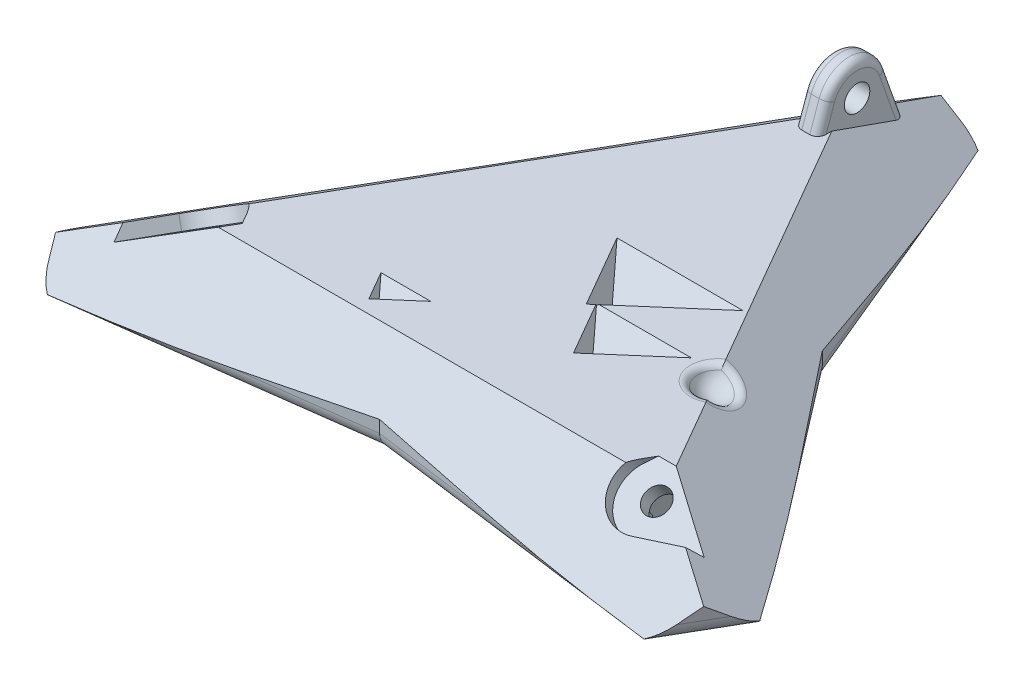
SolidWorks part; units mm, degrees
ref_plane "Front Plane" through (0, 0, 0) normal (0, 0, 1) x (1, 0, 0)
ref_plane "Top Plane" through (0, 0, 0) normal (0, 1, 0) x (1, 0, 0)
ref_plane "Right Plane" through (0, 0, 0) normal (1, 0, 0) x (0, 0, -1)
sketch "Sketch2" plane through (0, 0, 0) normal (0, 1, 0) x (1, 0, 0)
  line L0 (0, 57.735) -> (-50, -28.8675)
  line L1 (-50, -28.8675) -> (50, -28.8675)
  line L2 (50, -28.8675) -> (0, 57.735)
  line L3 (0, 0) -> (0, 57.735) construction
  line L4 (50, -28.8675) -> (0, 0) construction
  line L5 (0, 0) -> (-50, -28.8675) construction
  line L6 (0, 0) -> (0, -28.8675) construction
  line L7 (0, 0) -> (25, 14.4338) construction
  line L8 (0, 0) -> (-25, 14.4338) construction
  line L9 (10, 40.4145) -> (0, 34.641) construction
  line L10 (0, 34.641) -> (-10, 40.4145) construction
  dimension "D1" = 20
sketch "Sketch3" plane through (0, 0, 0) normal (1, 0, 0) x (0, 0, -1)
  line L0 (-28.8675, 0) -> (-19.245, 27.2166) construction
  line L1 (-19.245, 27.2166) -> (0, 20.4124) construction
  line L2 (0, 20.4124) -> (-28.8675, 0) construction
  line L3 (-19.245, 27.2166) -> (-28.983, -0.3266) construction
  line L4 (-28.983, -0.3266) -> (0.2309, 20.3308)
  line L5 (0.2309, 20.3308) -> (-19.245, 27.2166)
  line L6 (-28.983, -0.3266) -> (-28.983, 27.2166)
  line L7 (-28.983, 27.2166) -> (-19.245, 27.2166)
  line L8 (0, 0) -> (0, 103.8474) construction
  dimension "D1" = 0.2
ref_plane "Plane1" through (0, 0, 0) normal (0.5, 0, 0.866) x (0.866, 0, -0.5)
sketch "Sketch4" plane through (0, 0, 0) normal (0.5, 0, 0.866) x (0.866, 0, -0.5)
  line L0 (0, 20.4124) -> (19.245, 27.2166) construction
  line L1 (19.245, 27.2166) -> (28.8675, 0) construction
  line L2 (28.8675, 0) -> (0, 20.4124) construction
  line L3 (0, 81.6497) -> (0, 0) construction
  line L4 (-0.2309, 20.3308) -> (19.245, 27.2166)
  line L5 (19.245, 27.2166) -> (28.983, -0.3266) construction
  line L6 (28.983, -0.3266) -> (-0.2309, 20.3308)
  line L7 (19.245, 27.2166) -> (28.983, 27.2166)
  line L8 (28.983, 27.2166) -> (28.983, -0.3266)
  dimension "D1" = 0.2
ref_plane "Plane2" through (0, 0, 0) normal (0.5, 0, -0.866) x (-0.866, 0, -0.5)
sketch "Sketch5" plane through (0, 0, 0) normal (0.5, 0, -0.866) x (-0.866, 0, -0.5)
  line L0 (19.245, 27.2166) -> (0, 20.4124) construction
  line L1 (0, 20.4124) -> (28.8675, 0) construction
  line L2 (28.8675, 0) -> (19.245, 27.2166) construction
  line L3 (19.245, 27.2166) -> (-0.2309, 20.3308)
  line L4 (-0.2309, 20.3308) -> (28.983, -0.3266)
  line L5 (28.983, -0.3266) -> (19.245, 27.2166) construction
  line L6 (19.245, 27.2166) -> (28.983, 27.2166)
  line L7 (28.983, 27.2166) -> (28.983, -0.3266)
  dimension "D1" = 0.2
extrude "Boss-Extrude1" add sketch "Sketch2" along normal up to vertex (20.4124 mm away) up to point (0, 20.4124, 0)
extrude "Cut-Extrude2" cut sketch "Sketch3" against normal up to vertex (50 mm away) from vertex at 50 starting at point (50, 0, 28.8675)
extrude "Cut-Extrude3" cut sketch "Sketch4" along normal through all and the other way through all
extrude "Cut-Extrude4" cut sketch "Sketch5" along normal through all from vertex at -50 starting at point (-50, 0, 28.8675)
sketch "Sketch6" plane through (0, 0, 0) normal (0, 1, 0) x (1, 0, 0)
  line L0 (0, 0) -> (40.7397, -23.5211) construction
  line L1 (0, 0) -> (-40.7397, -23.5211) construction
  line L2 (0, 0) -> (0, -23.5211) construction
  line L3 (0, 0) -> (0, 47.0422) construction
  line L4 (0, 0) -> (-20.3699, 11.7606) construction
  line L5 (0, 0) -> (20.3699, 11.7606) construction
  line L6 (0, 0) -> (25, 14.4338) construction
  line L7 (50, -28.8675) -> (0, 0) construction
  line L8 (49.4, -28.5211) -> (0, 57.0422) construction
  line L9 (40.7397, -23.5211) -> (37.853, -28.5211) construction
  line L10 (0, 57.0422) -> (-49.4, -28.5211) construction
  line L11 (-49.4, -28.5211) -> (49.4, -28.5211) construction
  line L12 (37.853, -28.5211) -> (0, -23.5211)
  line L13 (0, -23.5211) -> (-37.853, -28.5211)
  line L14 (-37.853, -28.5211) -> (-40.7397, -23.5211) construction
  line L15 (-40.7397, -23.5211) -> (-43.6265, -18.5211) construction
  line L16 (-43.6265, -18.5211) -> (-20.3699, 11.7606)
  line L18 (5.7735, 47.0422) -> (-5.7735, 47.0422)
  line L19 (-37.853, -28.5211) -> (-43.6265, -18.5211)
  line L21 (20.3699, 11.7606) -> (43.6265, -18.5211)
  line L22 (43.6265, -18.5211) -> (40.7397, -23.5211) construction
  line L23 (0, 57.0422) -> (49.4, -28.5211) construction
  line L24 (0, 0) -> (0, 57.735) construction
  line L27 (43.6265, -18.5211) -> (37.853, -28.5211)
  line L35 (50, -28.8675) -> (0, 57.735) construction
  line L36 (50, -28.8675) -> (0, 57.735) construction
  line L37 (0, 57.735) -> (-50, -28.8675) construction
  line L38 (0, 57.735) -> (-50, -28.8675) construction
  line L46 (20.3699, 11.7606) -> (5.7735, 47.0422)
  line L47 (-5.7735, 47.0422) -> (-20.3699, 11.7606)
  circle A0 centre (0, 0) radius 47.0422 construction
  circle A1 centre (0, 0) radius 23.5211 construction
  circle A2 centre (0, 0) radius 57.0422 construction
  dimension "D1" = 10
  dimension "D2" = 5
extrude "Cut-Extrude5" cut sketch "Sketch6" along normal through all flip side to cut
sketch "Sketch7" plane through (0, 0, 0) normal (1, 0, 0) x (0, 0, -1)
  line L0 (31.2288, 11.3333) -> (27.2218, 0) construction
  line L1 (35.7071, 0) -> (27.2218, 0) construction
  line L3 (31.2288, 11.3333) -> (27.2218, 0)
  line L4 (42.7782, 0) -> (27.2218, 0)
  line L5 (38.7712, 11.3333) -> (42.7782, 0)
  line L6 (35, 10) -> (35, 0) construction
  arc A0 (38.7712, 8.6667) -> (31.2288, 11.3333) centre (35, 10) ccw construction
  arc A1 (38.7712, 11.3333) -> (31.2288, 11.3333) centre (35, 10) ccw
  circle A2 centre (35, 10) radius 1.6 construction
  circle A3 centre (35, 10) radius 1.6 construction
  circle A4 centre (35, 10) radius 4 construction
  circle A5 centre (35, 10) radius 4 construction
sketch "Sketch8" plane through (0, 0, 0) normal (0, 1, 0) x (1, 0, 0)
  line L0 (0, 27.2218) -> (0, 42.7782) construction
  line L1 (-1.5, 27.2218) -> (1.5, 27.2218)
  line L2 (-1.5, 27.2218) -> (-1.5, 42.7782)
  line L3 (-1.5, 42.7782) -> (1.5, 42.7782)
  line L4 (1.5, 27.2218) -> (1.5, 42.7782)
  line L5 (0, 31.4645) -> (-1.5, 31.4645) construction
  line L6 (0, 31.4645) -> (1.5, 31.4645) construction
  line L7 (3.7, 27.2218) -> (3.9, 27.2218) construction
  line L8 (1.8, 27.2218) -> (3.7, 27.2218)
  line L9 (1.8, 27.2218) -> (1.8, 42.7782)
  line L10 (1.8, 42.7782) -> (3.7, 42.7782)
  line L11 (3.7, 27.2218) -> (3.7, 42.7782)
  line L12 (-1.8, 27.2218) -> (-3.7, 27.2218)
  line L13 (-1.8, 27.2218) -> (-1.8, 42.7782)
  line L14 (-1.8, 42.7782) -> (-3.7, 42.7782)
  line L15 (-3.7, 27.2218) -> (-3.7, 42.7782)
  line L16 (3.9, 27.2218) -> (3.9, 42.7782) construction
  line L17 (3.9, 42.7782) -> (3.7, 42.7782) construction
  line L18 (-3.7, 42.7782) -> (-3.9, 42.7782) construction
  line L19 (-3.9, 42.7782) -> (-3.9, 27.2218) construction
  line L20 (-3.9, 27.2218) -> (-3.7, 27.2218) construction
  line L21 (-1.8, 27.2218) -> (-1.5, 27.2218) construction
  line L22 (1.8, 27.2218) -> (1.5, 27.2218) construction
  line L23 (-1.8, 42.7782) -> (-1.5, 42.7782) construction
  line L24 (1.5, 42.7782) -> (1.8, 42.7782) construction
  dimension "D1" = 3
  dimension "D2" = 0.3
  dimension "D3" = 0.2
  dimension "D4" = 1.9
ref_plane "Plane3" through (0, 8, 0) normal (0, 1, 0) x (1, 0, 0)
sketch "Sketch10" plane through (0, 8, 0) normal (0, 1, 0) x (1, 0, 0)
  circle A0 centre (0, 0) radius 57.0422 construction
  circle A1 centre (0, 0) radius 57.0422
extrude "Cut-Extrude7" cut sketch "Sketch10" along normal through all
extrude "Boss-Extrude2" add sketch "Sketch7" along normal up to vertex (1.5 mm away) and the other way up to vertex (1.5 mm away) up to point (1.5, 0, -42.7782) other way up to point (-1.5, 0, -42.7782)
sketch "Sketch9" plane through (0, 0, 0) normal (1, 0, 0) x (0, 0, -1)
  circle A0 centre (35, 10) radius 1.6 construction
  circle A1 centre (35, 10) radius 1.6
extrude "Cut-Extrude6" cut sketch "Sketch9" against normal through all and the other way through all
fillet "Fillet1" radius 2 9 edges at (40.7397, 0, 23.5211) (18.9265, 0, 26.0211) (-18.9265, 0, 26.0211) (-40.7397, 0, 23.5211) (-31.9982, 0, 3.3803) (-13.0717, 0, -29.4014) (0, 0, -47.0422) (31.9982, 0, 3.3803) (13.0717, 0, -29.4014)
fillet "Fillet2" radius 1 6 edges at (-1.5, 8.0235, -39.9414) (-1.5, 9.6667, -30.6395) (1.5, 8.0235, -39.9414) (1.5, 9.6667, -30.6395) (-1.5, 14, -35) (1.5, 14, -35)
ref_plane "Plane7" through (3.7, 0, 0) normal (1, 0, 0) x (0, 0, -1)
sketch "Sketch15" plane through (3.7, 0, 0) normal (1, 0, 0) x (0, 0, -1)
  circle A1 centre (35, 10) radius 2.85 construction
  circle A2 centre (35, 10) radius 2.85 construction
  circle A3 centre (35, 10) radius 3.15
  dimension "D1" = 0.3
ref_plane "Plane8" through (-3.7, 0, 0) normal (1, 0, 0) x (0, 0, -1)
sketch "Sketch16" plane through (-3.7, 0, 0) normal (1, 0, 0) x (0, 0, -1)
  line L0 (33.2391, 13.05) -> (31.4782, 10)
  line L1 (31.4782, 10) -> (33.2391, 6.95)
  line L2 (33.2391, 6.95) -> (36.7609, 6.95)
  line L3 (36.7609, 6.95) -> (38.5218, 10)
  line L4 (38.5218, 10) -> (36.7609, 13.05)
  line L5 (36.7609, 13.05) -> (33.2391, 13.05)
  line L6 (38.1754, 10) -> (36.5877, 12.75)
  line L7 (36.5877, 12.75) -> (33.4123, 12.75)
  line L8 (33.4123, 12.75) -> (31.8246, 10)
  line L9 (31.8246, 10) -> (33.4123, 7.25)
  line L10 (33.4123, 7.25) -> (36.5877, 7.25)
  line L11 (36.5877, 7.25) -> (38.1754, 10)
  line L12 (38.1754, 10) -> (36.5877, 12.75) construction
  line L13 (36.5877, 12.75) -> (33.4123, 12.75) construction
  line L14 (33.4123, 12.75) -> (31.8246, 10) construction
  line L15 (31.8246, 10) -> (33.4123, 7.25) construction
  line L16 (33.4123, 7.25) -> (36.5877, 7.25) construction
  line L17 (36.5877, 7.25) -> (38.1754, 10) construction
  dimension "D1" = 0
  dimension "D2" = 0.3
sketch "Sketch17" plane through (0, 8, 0) normal (0, 1, 0) x (1, 0, 0)
  line L0 (-10, 10.75) -> (-10, 20.75) construction
  line L1 (10, 20.75) -> (-10, 20.75) construction
  line L2 (10, 10.75) -> (10, 20.75) construction
  line L3 (10, 10.75) -> (-10, 10.75) construction
  line L4 (-10, 10.75) -> (-10, 20.75)
  line L5 (10, 20.75) -> (-10, 20.75)
  line L6 (10, 10.75) -> (10, 20.75)
  line L7 (10, 10.75) -> (-10, 10.75)
  line L8 (-13.75, -9.8438) -> (-13.75, 10.1562) construction
  line L9 (-13.75, 10.1562) -> (-3.75, 10.1562) construction
  line L10 (-3.75, -9.8438) -> (-3.75, 10.1562) construction
  line L11 (-13.75, -9.8438) -> (-3.75, -9.8438) construction
  line L12 (-13.75, -9.8438) -> (-13.75, 10.1562)
  line L13 (-13.75, 10.1562) -> (-3.75, 10.1562)
  line L14 (-3.75, -9.8438) -> (-3.75, 10.1562)
  line L15 (-13.75, -9.8438) -> (-3.75, -9.8438)
  line L16 (7, -9.8438) -> (7, 10.1562) construction
  line L17 (-3, 10.1562) -> (7, 10.1562) construction
  line L18 (-3, -9.8438) -> (-3, 10.1562) construction
  line L19 (-3, -9.8438) -> (7, -9.8438) construction
  line L20 (7, -9.8438) -> (7, 10.1562)
  line L21 (-3, 10.1562) -> (7, 10.1562)
  line L22 (-3, -9.8438) -> (-3, 10.1562)
  line L23 (-3, -9.8438) -> (7, -9.8438)
  line L25 (12.75, 10.1562) -> (7.75, 10.1562)
  line L26 (12.75, 10.1562) -> (12.75, -9.8438)
  line L27 (12.75, -9.8438) -> (7.75, -9.8438)
  line L28 (7.75, 10.1562) -> (7.75, -9.8438)
  line L29 (10, -10.25) -> (-10, -10.25)
  line L30 (10, -10.25) -> (10, -15.25)
  line L31 (10, -15.25) -> (-10, -15.25)
  line L32 (-10, -10.25) -> (-10, -15.25)
sketch "Sketch18" plane through (0, 27.2166, 19.245) normal (0.5, -0.8165, 0.2887) x (-0.866, -0.4714, 0.1667)
  line L0 (30.9459, 11.4333) -> (26.7976, -0.3)
  line L1 (26.7976, -0.3) -> (43.2024, -0.3)
  line L2 (43.2024, -0.3) -> (39.0541, 11.4333)
  line L3 (31.2288, 11.3333) -> (27.2218, 0)
  line L4 (27.2218, 0) -> (42.7782, 0)
  line L5 (42.7782, 0) -> (38.7712, 11.3333)
  line L6 (31.2288, 11.3333) -> (27.2218, 0) construction
  line L7 (27.2218, 0) -> (42.7782, 0) construction
  line L8 (42.7782, 0) -> (38.7712, 11.3333) construction
  arc A0 (39.0541, 11.4333) -> (30.9459, 11.4333) centre (35, 10) ccw
  arc A1 (38.7712, 11.3333) -> (31.2288, 11.3333) centre (35, 10) ccw
  arc A2 (38.7712, 11.3333) -> (31.2288, 11.3333) centre (35, 10) ccw construction
  dimension "D1" = 0
  dimension "D2" = 0.3
extrude "Cut-Extrude8" cut sketch "Sketch18" along normal up to vertex
sketch "Sketch19" plane through (0, 27.2166, 19.245) normal (0.5, -0.8165, 0.2887) x (-0.866, -0.4714, 0.1667)
  circle A0 centre (35, 10) radius 1.6 construction
  circle A1 centre (35, 10) radius 1.6
extrude "Cut-Extrude9" cut sketch "Sketch19" along normal through all
sketch "Sketch20" plane through (1.85, 24.1955, 20.3131) normal (0.5, -0.8165, 0.2887) x (-0.866, -0.4714, 0.1667)
  circle A1 centre (35, 10) radius 3.15
  circle A2 centre (35, 10) radius 3.15
  dimension "D1" = 0
extrude "Cut-Extrude10" cut sketch "Sketch20" along normal through all
sketch "Sketch21" plane through (16.6667, 27.2166, -9.6225) normal (0, -0.8165, -0.5774) x (0.5774, -0.4714, 0.6667)
  line L0 (30.9459, 11.4333) -> (26.7976, -0.3)
  line L1 (26.7976, -0.3) -> (43.2024, -0.3)
  line L2 (43.2024, -0.3) -> (39.0541, 11.4333)
  line L3 (31.2288, 11.3333) -> (27.2218, 0)
  line L4 (27.2218, 0) -> (42.7782, 0)
  line L5 (42.7782, 0) -> (38.7712, 11.3333)
  line L6 (31.2288, 11.3333) -> (27.2218, 0) construction
  line L7 (27.2218, 0) -> (42.7782, 0) construction
  line L8 (42.7782, 0) -> (38.7712, 11.3333) construction
  arc A1 (38.7712, 11.3333) -> (31.2288, 11.3333) centre (35, 10) ccw
  arc A2 (38.7712, 11.3333) -> (31.2288, 11.3333) centre (35, 10) ccw construction
  arc A3 (39.0541, 11.4333) -> (30.9459, 11.4333) centre (35, 10) ccw
  dimension "D1" = 0
  dimension "D2" = 0.3
extrude "Cut-Extrude11" cut sketch "Sketch21" along normal up to vertex
sketch "Sketch22" plane through (16.6667, 27.2166, -9.6225) normal (0, -0.8165, -0.5774) x (0.5774, -0.4714, 0.6667)
  circle A0 centre (35, 10) radius 1.6 construction
  circle A1 centre (35, 10) radius 1.6
extrude "Cut-Extrude12" cut sketch "Sketch22" along normal through all
sketch "Sketch23" plane through (16.6667, 24.1955, -11.7587) normal (0, -0.8165, -0.5774) x (0.5774, -0.4714, 0.6667)
  line L6 (33.2391, 13.05) -> (31.4782, 10)
  line L7 (31.4782, 10) -> (33.2391, 6.95)
  line L8 (33.2391, 6.95) -> (36.7609, 6.95)
  line L9 (36.7609, 6.95) -> (38.5218, 10)
  line L10 (38.5218, 10) -> (36.7609, 13.05)
  line L11 (36.7609, 13.05) -> (33.2391, 13.05)
  line L12 (33.2391, 13.05) -> (31.4782, 10)
  line L13 (31.4782, 10) -> (33.2391, 6.95)
  line L14 (33.2391, 6.95) -> (36.7609, 6.95)
  line L15 (36.7609, 6.95) -> (38.5218, 10)
  line L16 (38.5218, 10) -> (36.7609, 13.05)
  line L17 (36.7609, 13.05) -> (33.2391, 13.05)
  dimension "D1" = 0
extrude "Cut-Extrude13" cut sketch "Sketch23" along normal through all
ref_plane "Plane9" through (0, 10.9547, 7.7461) normal (0, -0.8165, -0.5774) x (-1, 0, 0)
sketch "Sketch24" plane through (0, 10.9547, 7.7461) normal (0, -0.8165, -0.5774) x (-1, 0, 0)
  line L0 (19.7955, 7.5855) -> (-5.5159, 25.4834) construction
  line L1 (9.2228, -7.3665) -> (19.7955, 7.5855) construction
  line L2 (-16.0886, 10.5314) -> (9.2228, -7.3665) construction
  line L3 (19.7955, 7.5855) -> (-5.5159, 25.4834) construction
  line L4 (9.2228, -7.3665) -> (19.7955, 7.5855) construction
  line L5 (-16.0886, 10.5314) -> (9.2228, -7.3665) construction
  line L6 (-16.0886, 10.5314) -> (-5.5159, 25.4834) construction
  line L7 (-16.7855, 10.4118) -> (9.3424, -8.0634)
  line L8 (9.3424, -8.0634) -> (20.4924, 7.7051)
  line L9 (20.4924, 7.7051) -> (-5.6355, 26.1803)
  line L10 (-16.7855, 10.4118) -> (-5.6355, 26.1803)
  dimension "D1" = 0.5
extrude "Cut-Extrude14" cut sketch "Sketch24" against normal through all
ref_plane "Plane10" through (0, 2.1773, 1.5396) normal (0, -0.8165, -0.5774) x (-1, 0, 0)
sketch "Sketch25" plane through (0, 2.1773, 1.5396) normal (0, -0.8165, -0.5774) x (-1, 0, 0)
  line L0 (-5.5159, 25.4834) -> (5.6701, 17.5737) construction
  line L1 (-4.9026, 2.6217) -> (-16.0886, 10.5314) construction
  line L2 (5.6701, 17.5737) -> (-4.9026, 2.6217) construction
  line L3 (-5.5159, 25.4834) -> (5.6701, 17.5737)
  line L4 (-4.9026, 2.6217) -> (-16.0886, 10.5314)
  line L5 (5.6701, 17.5737) -> (-4.9026, 2.6217)
  line L6 (-16.0886, 10.5314) -> (-5.5159, 25.4834)
extrude "Cut-Extrude15" cut sketch "Sketch25" against normal through all
ref_plane "Plane11" through (4.2594, -3.4778, 4.9183) normal (0.5774, -0.4714, 0.6667) x (0.8165, 0.3333, -0.4714)
sketch "Sketch26" plane through (4.2594, -3.4778, 4.9183) normal (0.5774, -0.4714, 0.6667) x (0.8165, 0.3333, -0.4714)
  line L0 (6.3166, 7.5105) -> (19.2166, 7.5105) construction
  line L1 (6.3166, 25.8229) -> (6.3166, 7.5105) construction
  line L2 (19.2166, 25.8229) -> (6.3166, 25.8229) construction
  line L3 (6.3166, 7.5105) -> (19.2166, 7.5105)
  line L4 (6.3166, 25.8229) -> (6.3166, 7.5105)
  line L5 (19.2166, 25.8229) -> (6.3166, 25.8229)
  line L6 (19.2166, 7.5105) -> (19.2166, 25.8229)
extrude "Cut-Extrude16" cut sketch "Sketch26" against normal through all
sketch "Sketch27" plane through (15.6902, 6.4055, -9.0588) normal (-0.8165, -0.3333, 0.4714) x (0.4364, 0.1782, 0.8819)
  line L0 (10.4082, -0.2611) -> (15.9082, -0.2611)
  arc A0 (10.4082, -0.2611) -> (15.9082, -0.2611) centre (13.1582, -0.2611) ccw
  circle A1 centre (13.1582, -0.2611) radius 0.75 construction
  ellipse E0 centre (13.1582, -0.2611) end of major axis (12.3947, 0.4) minor radius 0.75 (14.0561, -0.6301) -> (13.6492, 0.3058) ccw construction
  dimension "D1" = 2
revolve "Cut-Revolve1" cut sketch "Sketch27" angle 360 about L0
fillet "Fillet3" radius 1 2 edges at (23.1867, 6.5308, 1.5901) (19.1911, 8, 3.897)
fillet "Fillet4" radius 1 7 edges at (31.4791, 0, 14.7666) (31.1993, 0, 11.0469) (28.4291, 0, 9.4838) (25.9388, 0, 11.6405) (26.2186, 0, 15.3602) (28.9888, 0, 16.9233) (-29.1302, 0, 16.3319)
